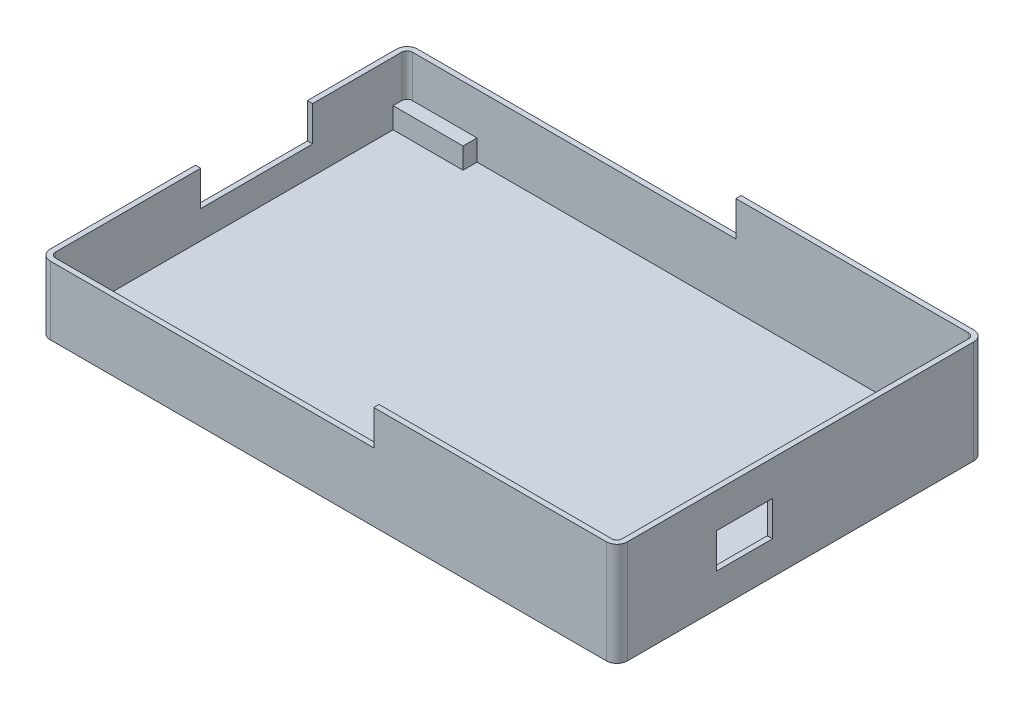
SolidWorks part; units mm, degrees
ref_plane "Front Plane" through (0, 0, 0) normal (0, 0, 1) x (1, 0, 0)
ref_plane "Top Plane" through (0, 0, 0) normal (0, 1, 0) x (1, 0, 0)
ref_plane "Right Plane" through (0, 0, 0) normal (1, 0, 0) x (0, 0, -1)
sketch "Sketch1" plane through (0, 0, 0) normal (0, 1, 0) x (1, 0, 0)
  line L0 (0, 49) -> (10, 49)
  line L1 (0.75, 0) -> (80.25, 0)
  line L2 (0, 0.75) -> (0, 50.25)
  line L3 (0.75, 51) -> (80.25, 51)
  line L4 (81, 0.75) -> (81, 50.25)
  line L5 (0.75, 51.75) -> (80.25, 51.75)
  line L6 (-0.75, 50.25) -> (-0.75, 0.75)
  line L7 (0.75, -0.75) -> (80.25, -0.75)
  line L8 (81.75, 50.25) -> (81.75, 0.75)
  line L9 (10, 49) -> (10, 51)
  line L10 (0, 2) -> (10, 2)
  line L11 (10, 2) -> (10, 0)
  line L12 (71, 51) -> (71, 49)
  line L13 (71, 49) -> (81, 49)
  line L14 (81, 2) -> (71, 2)
  line L15 (71, 2) -> (71, 0)
  line L16 (-0.75, 37.5) -> (0, 37.5)
  line L17 (-0.75, 21.5) -> (0, 21.5)
  line L18 (81, 13.5) -> (81.75, 13.5)
  line L19 (81, 21.5) -> (81.75, 21.5)
  line L20 (47, 51.75) -> (47, 51)
  line L21 (47, 0) -> (47, -0.75)
  arc A0 (0.75, 51) -> (0, 50.25) centre (0.75, 50.25) ccw
  arc A1 (0, 0.75) -> (0.75, 0) centre (0.75, 0.75) ccw
  arc A2 (80.25, 0) -> (81, 0.75) centre (80.25, 0.75) ccw
  arc A3 (80.25, 51) -> (81, 50.25) centre (80.25, 50.25) cw
  arc A4 (-0.75, 0.75) -> (0.75, -0.75) centre (0.75, 0.75) ccw
  arc A5 (80.25, -0.75) -> (81.75, 0.75) centre (80.25, 0.75) ccw
  arc A6 (81.75, 50.25) -> (80.25, 51.75) centre (80.25, 50.25) ccw
  arc A7 (0.75, 51.75) -> (-0.75, 50.25) centre (0.75, 50.25) ccw
  point P11 (0, 51)
  point P14 (0, 0)
  point P19 (81, 51)
  dimension "D7" = 0.75
  dimension "D8" = 1.5
  dimension "D1" = 51
  dimension "D2" = 81
  dimension "D3" = 0.75
  dimension "D4" = 0.75
  dimension "D5" = 0.75
  dimension "D6" = 0.75
  dimension "D9" = 2
  dimension "D10" = 10
  dimension "D11" = 13.5
  dimension "D12" = 16
  dimension "D13" = 13.5
  dimension "D14" = 8
  dimension "D15" = 47
extrude "Boss-Extrude1" add sketch "Sketch1" along normal blind 0.75 contours L6 A4 L7 A5 L8 A6 L5 A7
extrude "Boss-Extrude2" add sketch "Sketch1<3>" along normal blind 3.75 contours L2 A1 L1 L11 L10 | L3 A0 L2 L0 L9 | A3 L3 L12 L13 L4 | L1 A2 L4 L14 L15 region at (5.0293, 0, -49.9949) region at (5.0293, 0, -1.0051) region at (75.9707, 0, -49.9949) region at (75.9707, 0, -1.0051)
sketch "Sketch1<3>" plane through (0, 0, 0) normal (0, 1, 0) x (1, 0, 0) same geometry as "Sketch1"
extrude "Boss-Extrude3" add sketch "Sketch1<4>" along normal blind 9.75 contours L6 A4 L7 L21 L1 A1 L2 L17 | L7 A5 L8 L18 L4 A2 L1 L21 | L8 A6 L5 L20 L3 A3 L4 L19 | L5 A7 L6 L16 L2 A0 L3 L20 region at (-0.4983, 0, -43.25) region at (-0.5268, 0, -11.75) region at (47.4607, 0, -51.375) region at (59, 0, 0.3756)
sketch "Sketch1<4>" plane through (0, 0, 0) normal (0, 1, 0) x (1, 0, 0) same geometry as "Sketch1"
extrude "Boss-Extrude4" add sketch "Sketch1<5>" along normal blind 4.75 contours L6 L17 L2 L16 | L19 L4 L18 L8 region at (-0.375, 0, -29.5) region at (81.375, 0, -17.5)
sketch "Sketch1<5>" plane through (0, 0, 0) normal (0, 1, 0) x (1, 0, 0) same geometry as "Sketch1"
extrude "Boss-Extrude5" add sketch "Sketch1<8>" along normal blind 5 from offset 9.75 contours L7 A5 L8 L18 L4 A2 L1 L21 | L19 L4 L18 L8 | L8 A6 L5 L20 L3 A3 L4 L19 region at (47.4607, 0, -51.375) region at (59, 0, 0.3756) region at (81.375, 0, -17.5)
sketch "Sketch1<8>" plane through (0, 0, 0) normal (0, 1, 0) x (1, 0, 0) same geometry as "Sketch1"
